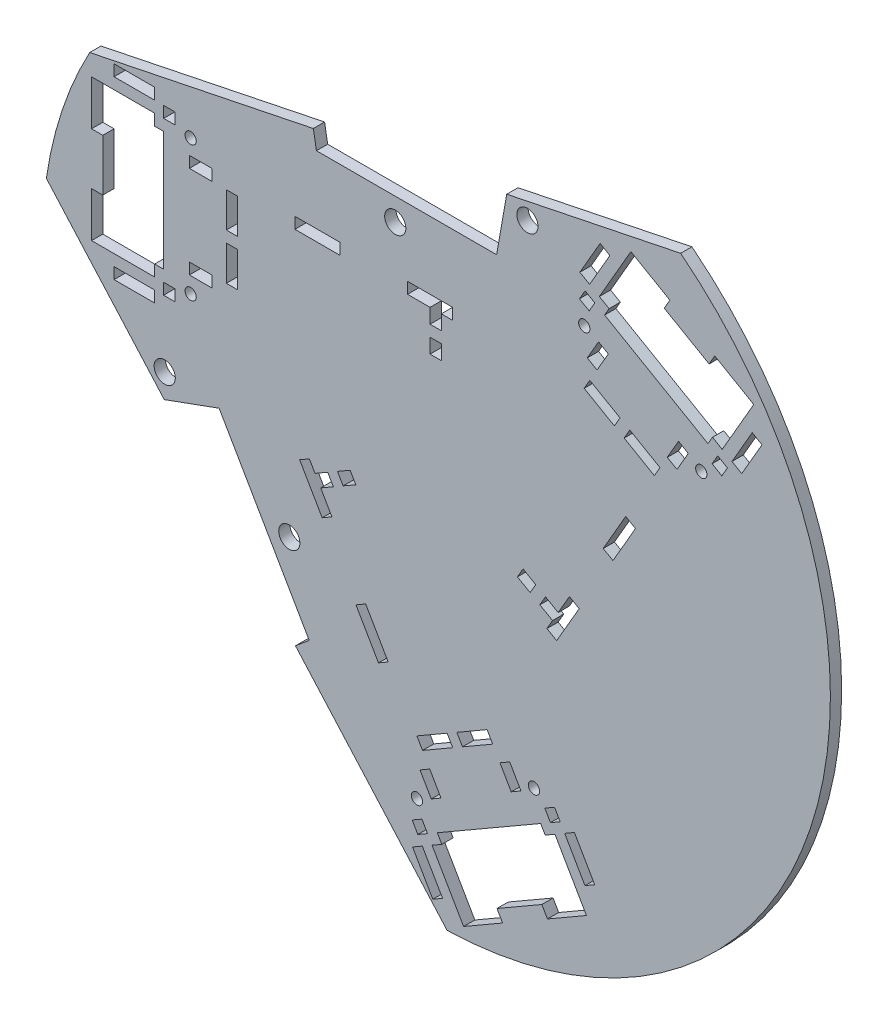
SolidWorks part; units mm, degrees
material "Balsa"
ref_plane "Plan de face" through (0, 0, 0) normal (0, 0, 1) x (1, 0, 0)
ref_plane "Plan de dessus" through (0, 0, 0) normal (0, 1, 0) x (1, 0, 0)
ref_plane "Plan de droite" through (0, 0, 0) normal (1, 0, 0) x (0, 0, -1)
sketch "Esquisse1" plane through (0, 0, 0) normal (0, 0, 1) x (1, 0, 0)
  circle A0 centre (148.0804, -12.1102) radius 175
extrude "Boss.-Extru.1" add sketch "Esquisse1" along normal blind 5
sketch "Esquisse2" plane through (0, 0, 0) normal (0, 0, -1) x (-1, 0, 0)
  line L0 (-155.3118, 53.7774) -> (-135.3118, 53.7774)
  line L1 (-150.3118, 37.2774) -> (-145.3118, 37.2774)
  line L2 (-150.3118, 37.2774) -> (-150.3118, 30.7774)
  line L3 (-150.3118, 30.7774) -> (-145.3118, 30.7774)
  line L4 (-145.3118, 37.2774) -> (-145.3118, 30.7774)
  line L5 (-105.3118, 53.7774) -> (-85.3118, 53.7774)
  line L6 (-105.3118, 53.7774) -> (-105.3118, 48.7774)
  line L7 (-105.3118, 48.7774) -> (-85.3118, 48.7774)
  line L8 (-85.3118, 53.7774) -> (-85.3118, 48.7774)
  line L9 (-59.86, 48.7774) -> (-54.86, 48.7774)
  line L10 (-59.86, 48.7774) -> (-59.86, 33.2774)
  line L11 (-59.86, 33.2774) -> (-54.86, 33.2774)
  line L12 (-54.86, 48.7774) -> (-54.86, 33.2774)
  line L13 (-59.86, 28.2774) -> (-54.86, 28.2774)
  line L14 (-59.86, 28.2774) -> (-59.86, 12.7774)
  line L15 (-59.86, 12.7774) -> (-54.86, 12.7774)
  line L16 (-54.86, 28.2774) -> (-54.86, 12.7774)
  line L17 (-48.43, 12.7774) -> (-38.43, 12.7774)
  line L18 (-48.43, 12.7774) -> (-48.43, 7.7774)
  line L19 (-48.43, 7.7774) -> (-38.43, 7.7774)
  line L20 (-38.43, 12.7774) -> (-38.43, 7.7774)
  line L21 (-32, -0.7226) -> (-27, -0.7226)
  line L22 (-32, -0.7226) -> (-32, -5.7226)
  line L23 (-32, -5.7226) -> (-27, -5.7226)
  line L24 (-27, -0.7226) -> (-27, -5.7226)
  line L25 (-23, -5.7226) -> (-5, -5.7226)
  line L26 (-23, -5.7226) -> (-23, -10.7226)
  line L27 (-23, -10.7226) -> (-5, -10.7226)
  line L28 (-5, -5.7226) -> (-5, -10.7226)
  line L29 (0, -0.7226) -> (5, -0.7226)
  line L30 (0, -0.7226) -> (0, 19.2774)
  line L31 (0, 19.2774) -> (5, 19.2774)
  line L32 (5, -0.7226) -> (5, 19.2774)
  line L33 (0, 42.2774) -> (5, 42.2774)
  line L34 (0, 42.2774) -> (0, 62.2774)
  line L35 (0, 62.2774) -> (5, 62.2774)
  line L36 (5, 42.2774) -> (5, 62.2774)
  line L37 (-23, 67.2774) -> (-5, 67.2774)
  line L38 (-23, 67.2774) -> (-23, 72.2774)
  line L39 (-23, 72.2774) -> (-5, 72.2774)
  line L40 (-5, 67.2774) -> (-5, 72.2774)
  line L41 (-27, 67.2774) -> (-32, 67.2774)
  line L42 (-27, 67.2774) -> (-27, 62.2774)
  line L43 (-27, 62.2774) -> (-32, 62.2774)
  line L44 (-32, 67.2774) -> (-32, 62.2774)
  line L45 (-38.43, 53.7774) -> (-48.43, 53.7774)
  line L46 (-38.43, 53.7774) -> (-38.43, 48.7774)
  line L47 (-38.43, 48.7774) -> (-48.43, 48.7774)
  line L48 (-48.43, 53.7774) -> (-48.43, 48.7774)
  line L49 (-135.3118, 53.7774) -> (-135.3118, 48.7774)
  line L50 (-135.3118, 48.7774) -> (-145.3118, 48.7774)
  line L51 (-135.3118, 48.7774) -> (-155.3118, 48.7774) construction
  line L52 (-145.3118, 48.7774) -> (-145.3118, 42.2774)
  line L53 (-145.3118, 42.2774) -> (-150.3118, 42.2774)
  line L54 (-150.3118, 42.2774) -> (-150.3118, 48.7774)
  line L55 (-150.3118, 48.7774) -> (-155.3118, 48.7774)
  line L56 (-155.3118, 48.7774) -> (-155.3118, 53.7774)
  line L57 (-87.4044, -38.7914) -> (-97.4044, -56.1119)
  line L58 (-104.1938, -34.8716) -> (-106.6938, -39.2017)
  line L59 (-104.1938, -34.8716) -> (-109.823, -31.6216)
  line L60 (-109.823, -31.6216) -> (-112.323, -35.9517)
  line L61 (-106.6938, -39.2017) -> (-112.323, -35.9517)
  line L62 (-112.4044, -82.0927) -> (-122.4044, -99.4132)
  line L63 (-112.4044, -82.0927) -> (-116.7345, -79.5927)
  line L64 (-116.7345, -79.5927) -> (-126.7345, -96.9132)
  line L65 (-122.4044, -99.4132) -> (-126.7345, -96.9132)
  line L66 (-139.4604, -118.9551) -> (-141.9604, -123.2852)
  line L67 (-139.4604, -118.9551) -> (-152.8838, -111.2051)
  line L68 (-152.8838, -111.2051) -> (-155.3838, -115.5352)
  line L69 (-141.9604, -123.2852) -> (-155.3838, -115.5352)
  line L70 (-157.2139, -108.7051) -> (-159.7139, -113.0352)
  line L71 (-157.2139, -108.7051) -> (-170.6373, -100.9551)
  line L72 (-170.6373, -100.9551) -> (-173.1373, -105.2852)
  line L73 (-159.7139, -113.0352) -> (-173.1373, -105.2852)
  line L74 (-176.3523, -110.8538) -> (-181.3523, -119.514)
  line L75 (-176.3523, -110.8538) -> (-180.6825, -108.3538)
  line L76 (-180.6825, -108.3538) -> (-185.6825, -117.014)
  line L77 (-181.3523, -119.514) -> (-185.6825, -117.014)
  line L78 (-196.2587, -118.3326) -> (-198.7587, -122.6627)
  line L79 (-196.2587, -118.3326) -> (-200.5888, -115.8326)
  line L80 (-200.5888, -115.8326) -> (-203.0888, -120.1627)
  line L81 (-198.7587, -122.6627) -> (-203.0888, -120.1627)
  line L82 (-205.0888, -123.6268) -> (-214.0888, -139.2153)
  line L83 (-205.0888, -123.6268) -> (-209.4189, -121.1268)
  line L84 (-209.4189, -121.1268) -> (-218.4189, -136.7153)
  line L85 (-214.0888, -139.2153) -> (-218.4189, -136.7153)
  line L86 (-212.2587, -146.0454) -> (-214.7587, -150.3755)
  line L87 (-212.2587, -146.0454) -> (-194.9382, -156.0454)
  line L88 (-194.9382, -156.0454) -> (-197.4382, -160.3755)
  line L89 (-214.7587, -150.3755) -> (-197.4382, -160.3755)
  line L90 (-175.0196, -167.5454) -> (-177.5196, -171.8755)
  line L91 (-175.0196, -167.5454) -> (-157.6991, -177.5454)
  line L92 (-157.6991, -177.5454) -> (-160.1991, -181.8755)
  line L93 (-177.5196, -171.8755) -> (-160.1991, -181.8755)
  line L94 (-141.869, -160.1268) -> (-150.869, -175.7153)
  line L95 (-141.869, -160.1268) -> (-137.5388, -162.6268)
  line L96 (-137.5388, -162.6268) -> (-146.5388, -178.2153)
  line L97 (-150.869, -175.7153) -> (-146.5388, -178.2153)
  line L98 (-139.869, -156.6627) -> (-137.369, -152.3326)
  line L99 (-139.869, -156.6627) -> (-144.1991, -154.1627)
  line L100 (-144.1991, -154.1627) -> (-141.6991, -149.8326)
  line L101 (-137.369, -152.3326) -> (-141.6991, -149.8326)
  line L102 (-145.8453, -140.014) -> (-140.8453, -131.3538)
  line L103 (-145.8453, -140.014) -> (-150.1754, -137.514)
  line L104 (-150.1754, -137.514) -> (-145.1754, -128.8538)
  line L105 (-140.8453, -131.3538) -> (-145.1754, -128.8538)
  line L106 (-97.4044, -56.1119) -> (-101.7345, -53.6119)
  line L107 (-101.7345, -53.6119) -> (-96.7345, -44.9517)
  line L108 (-96.7345, -44.9517) -> (-102.3637, -41.7017)
  line L109 (-102.3637, -41.7017) -> (-99.8637, -37.3716)
  line L110 (-99.8637, -37.3716) -> (-94.2345, -40.6216)
  line L111 (-94.2345, -40.6216) -> (-91.7345, -36.2914)
  line L112 (-91.7345, -36.2914) -> (-87.4044, -38.7914)
  line L113 (-201.5251, -51.3165) -> (-211.5251, -33.996)
  line L114 (-189.7357, -38.7364) -> (-192.2357, -34.4063)
  line L115 (-189.7357, -38.7364) -> (-184.1065, -35.4864)
  line L116 (-184.1065, -35.4864) -> (-186.6065, -31.1563)
  line L117 (-192.2357, -34.4063) -> (-186.6065, -31.1563)
  line L118 (-226.5251, -8.0153) -> (-236.5251, 9.3053)
  line L119 (-226.5251, -8.0153) -> (-222.195, -5.5153)
  line L120 (-222.195, -5.5153) -> (-232.195, 11.8053)
  line L121 (-236.5251, 9.3053) -> (-232.195, 11.8053)
  line L122 (-244.9209, 33.8472) -> (-247.4209, 38.1773)
  line L123 (-244.9209, 33.8472) -> (-231.4975, 41.5972)
  line L124 (-231.4975, 41.5972) -> (-233.9975, 45.9273)
  line L125 (-247.4209, 38.1773) -> (-233.9975, 45.9273)
  line L126 (-227.1673, 44.0972) -> (-229.6673, 48.4273)
  line L127 (-227.1673, 44.0972) -> (-213.7439, 51.8472)
  line L128 (-213.7439, 51.8472) -> (-216.2439, 56.1773)
  line L129 (-229.6673, 48.4273) -> (-216.2439, 56.1773)
  line L130 (-219.4589, 61.7458) -> (-224.4589, 70.4061)
  line L131 (-219.4589, 61.7458) -> (-215.1288, 64.2458)
  line L132 (-215.1288, 64.2458) -> (-220.1288, 72.9061)
  line L133 (-224.4589, 70.4061) -> (-220.1288, 72.9061)
  line L134 (-215.9826, 82.7246) -> (-218.4826, 87.0547)
  line L135 (-215.9826, 82.7246) -> (-211.6525, 85.2246)
  line L136 (-211.6525, 85.2246) -> (-214.1525, 89.5547)
  line L137 (-218.4826, 87.0547) -> (-214.1525, 89.5547)
  line L138 (-216.1525, 93.0188) -> (-225.1525, 108.6073)
  line L139 (-216.1525, 93.0188) -> (-211.8223, 95.5188)
  line L140 (-211.8223, 95.5188) -> (-220.8223, 111.1073)
  line L141 (-225.1525, 108.6073) -> (-220.8223, 111.1073)
  line L142 (-231.9826, 110.4374) -> (-234.4826, 114.7676)
  line L143 (-231.9826, 110.4374) -> (-249.3031, 100.4374)
  line L144 (-249.3031, 100.4374) -> (-251.8031, 104.7676)
  line L145 (-234.4826, 114.7676) -> (-251.8031, 104.7676)
  line L146 (-269.2217, 88.9374) -> (-271.7217, 93.2676)
  line L147 (-269.2217, 88.9374) -> (-286.5422, 78.9374)
  line L148 (-286.5422, 78.9374) -> (-289.0422, 83.2676)
  line L149 (-271.7217, 93.2676) -> (-289.0422, 83.2676)
  line L150 (-279.3723, 56.5188) -> (-288.3723, 72.1073)
  line L151 (-279.3723, 56.5188) -> (-283.7025, 54.0188)
  line L152 (-283.7025, 54.0188) -> (-292.7025, 69.6073)
  line L153 (-288.3723, 72.1073) -> (-292.7025, 69.6073)
  line L154 (-277.3723, 53.0547) -> (-274.8723, 48.7246)
  line L155 (-277.3723, 53.0547) -> (-273.0422, 55.5547)
  line L156 (-273.0422, 55.5547) -> (-270.5422, 51.2246)
  line L157 (-274.8723, 48.7246) -> (-270.5422, 51.2246)
  line L158 (-259.966, 49.9061) -> (-254.966, 41.2458)
  line L159 (-259.966, 49.9061) -> (-255.6359, 52.4061)
  line L160 (-255.6359, 52.4061) -> (-250.6359, 43.7458)
  line L161 (-254.966, 41.2458) -> (-250.6359, 43.7458)
  line L162 (-211.5251, -33.996) -> (-207.195, -31.496)
  line L163 (-207.195, -31.496) -> (-202.195, -40.1563)
  line L164 (-202.195, -40.1563) -> (-196.5658, -36.9063)
  line L165 (-196.5658, -36.9063) -> (-194.0658, -41.2364)
  line L166 (-194.0658, -41.2364) -> (-199.695, -44.4864)
  line L167 (-199.695, -44.4864) -> (-197.195, -48.8165)
  line L168 (-197.195, -48.8165) -> (-201.5251, -51.3165)
  point P204 (-148.0804, -12.1102)
  dimension "D1" = 3
extrude "Enlèv. mat.-Extru.1" cut sketch "Esquisse2" against normal blind 5
sketch "Esquisse3" plane through (0, 0, 0) normal (0, 0, -1) x (-1, 0, 0)
  line L0 (-59.86, 33.2774) -> (-59.86, 28.2774) construction
  line L1 (-59.86, 30.7774) -> (32.4397, 30.7774) construction
  line L2 (0, -0.7226) -> (-23, -0.7226)
  line L3 (-23, -0.7226) -> (-23, 4.2774)
  line L4 (-23, 4.2774) -> (-27, 4.2774)
  line L5 (-23, 57.2774) -> (-27, 57.2774)
  line L6 (-23, 62.2774) -> (-23, 57.2774)
  line L7 (0, 62.2774) -> (-23, 62.2774)
  line L8 (-27, 57.2774) -> (-27, 4.2774)
  line L9 (0, -0.7226) -> (0, 62.2774)
  line L10 (-212.2587, -146.0454) -> (-200.7587, -126.1268)
  line L11 (-200.7587, -126.1268) -> (-196.4286, -128.6268)
  line L12 (-196.4286, -128.6268) -> (-194.4286, -125.1627)
  line L13 (-150.5292, -155.1268) -> (-148.5292, -151.6627)
  line L14 (-146.1991, -157.6268) -> (-150.5292, -155.1268)
  line L15 (-157.6991, -177.5454) -> (-146.1991, -157.6268)
  line L16 (-148.5292, -151.6627) -> (-194.4286, -125.1627)
  line L17 (-212.2587, -146.0454) -> (-157.6991, -177.5454)
  line L18 (-152.8838, -111.2051) -> (-157.2139, -108.7051) construction
  line L19 (-155.0489, -109.9551) -> (-201.1987, -189.889) construction
  line L20 (-231.9826, 110.4374) -> (-220.4826, 90.5188)
  line L21 (-220.4826, 90.5188) -> (-224.8127, 88.0188)
  line L22 (-224.8127, 88.0188) -> (-222.8127, 84.5547)
  line L23 (-270.7121, 61.5188) -> (-268.7121, 58.0547)
  line L24 (-275.0422, 59.0188) -> (-270.7121, 61.5188)
  line L25 (-286.5422, 78.9374) -> (-275.0422, 59.0188)
  line L26 (-268.7121, 58.0547) -> (-222.8127, 84.5547)
  line L27 (-231.9826, 110.4374) -> (-286.5422, 78.9374)
  line L28 (-231.4975, 41.5972) -> (-227.1673, 44.0972) construction
  line L29 (-229.3324, 42.8472) -> (-275.4822, 122.781) construction
  point P42 (-148.0804, -12.1102)
  dimension "D1" = 5
  dimension "D2" = 4
  dimension "D3" = 23
  dimension "D4" = 3
extrude "Enlèv. mat.-Extru.2" cut sketch "Esquisse3" against normal blind 5
sketch "Esquisse4" plane through (0, 0, 0) normal (0, 0, -1) x (-1, 0, 0)
  line L0 (-32, 67.2774) -> (-32, 62.2774) construction
  line L1 (-38.43, 53.7774) -> (-48.43, 53.7774) construction
  line L2 (-27, 30.7774) -> (-93.5454, 30.7774) construction
  line L3 (-27, 57.2774) -> (-27, 4.2774) construction
  line L4 (-171.4789, -138.4127) -> (-138.2062, -80.7827) construction
  line L5 (-245.7624, 71.3047) -> (-212.4897, 13.6748) construction
  circle A0 centre (-39, 60.7774) radius 2.5
  circle A1 centre (-39, 0.7774) radius 2.5
  circle A2 centre (-139.4981, -143.0204) radius 2.5
  circle A3 centre (-191.4596, -113.0204) radius 2.5
  circle A4 centre (-265.7432, 45.9124) radius 2.5
  circle A5 centre (-213.7816, 75.9124) radius 2.5
  point P27 (-148.0804, -12.1102)
  dimension "D1" = 7
  dimension "D2" = 7
  dimension "D3" = 3
extrude "Enlèv. mat.-Extru.3" cut sketch "Esquisse4" against normal blind 5
sketch "Esquisse5" plane through (0, 0, 0) normal (0, 0, -1) x (-1, 0, 0)
  line L0 (9.513, 70.4436) -> (-93.4749, 91.6327)
  line L1 (-315.6991, 137.3538) -> (-290.787, 258.4375)
  line L2 (-290.787, 258.4375) -> (34.4251, 191.5273)
  line L3 (34.4251, 191.5273) -> (9.513, 70.4436)
  line L5 (-179.3609, 109.3031) -> (-315.6991, 137.3538)
  line L6 (-94.86, 83.7774) -> (-174.86, 83.7774)
  line L7 (-174.86, 83.7774) -> (-179.3609, 109.3031)
  line L9 (-93.4749, 91.6327) -> (-94.86, 83.7774)
  line L10 (-155.3834, -189.8669) -> (-85.5392, -111.2714)
  line L11 (65.1685, 58.3199) -> (157.574, -23.7965)
  line L12 (26.9196, -12.1102) -> (-148.0804, -12.1102) construction
  line L13 (157.574, -23.7965) -> (-62.9779, -271.9834)
  line L14 (-62.9779, -271.9834) -> (-155.3834, -189.8669)
  line L16 (-27.2932, -45.7272) -> (65.1685, 58.3199)
  line L17 (-91.6495, -106.1442) -> (-51.6495, -36.8622)
  line L18 (-51.6495, -36.8622) -> (-27.2932, -45.7272)
  line L20 (-85.5392, -111.2714) -> (-91.6495, -106.1442)
  line L21 (-148.0804, -12.1102) -> (-235.5804, -163.6646) construction
  line L22 (-93.4749, 91.6327) -> (-179.3609, 109.3031) construction
  line L23 (-139.86, 83.7774) -> (-139.86, 101.1761) construction
  circle A0 centre (-188.5408, 103.7774) radius 4.7
  circle A1 centre (-129.86, 73.7774) radius 4.7
  circle A2 centre (-27.4886, -35.0143) radius 4.7
  circle A3 centre (-82.8098, -70.8333) radius 4.7
  point P15 (-148.0804, -12.1102)
  point P35 (-148.0804, -12.1102)
  dimension "D2" = 9.4
  dimension "D3" = 9.4
  dimension "D4" = 100
  dimension "D5" = 100
  dimension "D7" = 45
  dimension "D9" = 80
  dimension "D10" = 35
  dimension "D11" = 85.8876
  dimension "D12" = 58.6808
  dimension "D13" = 30
  dimension "D14" = 10
  dimension "D15" = 11.626
  dimension "D16" = 18.2204
  dimension "D18" = 17.3986
  dimension "D17" = 2
extrude "Enlèv. mat.-Extru.4" cut sketch "Esquisse5" against normal blind 5
